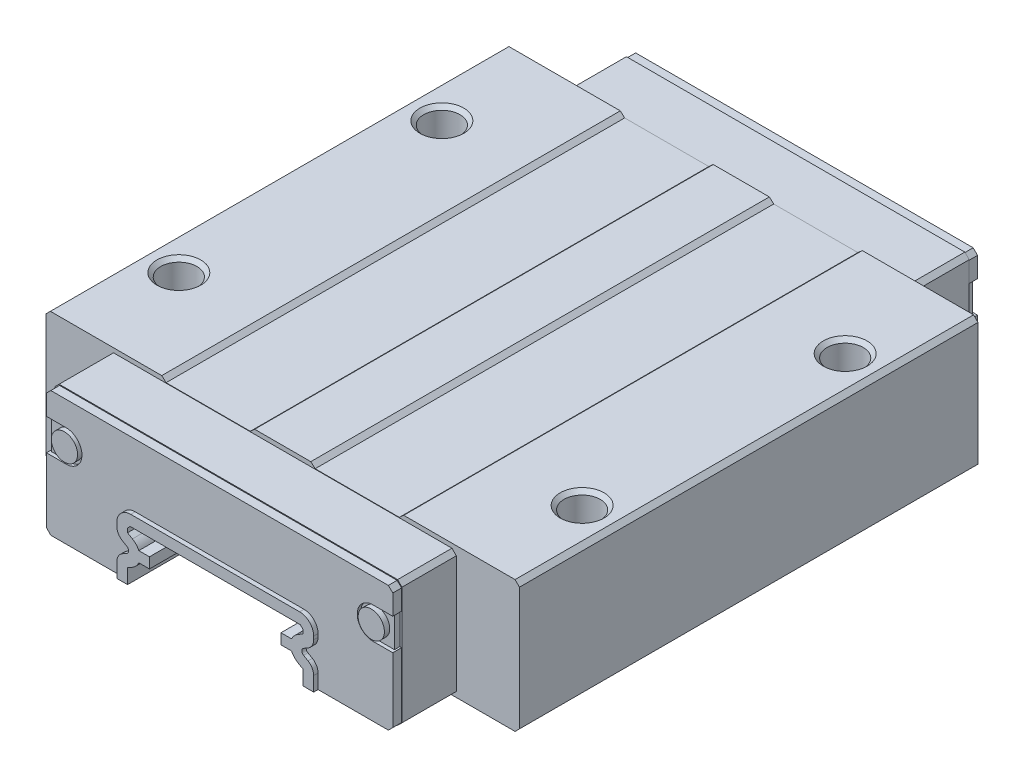
SolidWorks part; units mm, degrees
ref_plane "Front Plane" through (0, 0, 0) normal (0, 0, 1) x (1, 0, 0)
ref_plane "Top Plane" through (0, 0, 0) normal (0, 1, 0) x (1, 0, 0)
ref_plane "Right Plane" through (0, 0, 0) normal (1, 0, 0) x (0, 0, -1)
ref_plane "Plane1" through (0, 0, 0) normal (0, 0, 1) x (1, 0, 0)
sketch "Sketch1" plane through (0, 0, 0) normal (0, 0, 1) x (1, 0, 0)
  line L0 (-27, 19.5) -> (-27, 5.5)
  line L1 (-27, 5.5) -> (-26.5, 5)
  line L2 (-26.5, 5) -> (-14.4723, 5)
  line L3 (-14.4723, 5) -> (-14.2578, 5.1)
  line L4 (-14.2578, 5.1) -> (14.2578, 5.1)
  line L5 (14.2578, 5.1) -> (14.4723, 5)
  line L6 (14.4723, 5) -> (26.5, 5)
  line L7 (26.5, 5) -> (27, 5.5)
  line L8 (27, 5.5) -> (27, 19.5)
  line L9 (27, 19.5) -> (26.5, 20)
  line L10 (26.5, 20) -> (13.8, 20)
  line L11 (13.8, 20) -> (13.3, 19.55)
  line L12 (13.3, 19.55) -> (3.7, 19.55)
  line L13 (3.7, 19.55) -> (3.2, 20)
  line L14 (3.2, 20) -> (-3.2, 20)
  line L15 (-3.2, 20) -> (-3.7, 19.55)
  line L16 (-3.7, 19.55) -> (-13.3, 19.55)
  line L17 (-13.3, 19.55) -> (-13.8, 20)
  line L18 (-13.8, 20) -> (-26.5, 20)
  line L19 (-26.5, 20) -> (-27, 19.5)
extrude "Boss-Extrude1" add sketch "Sketch1" against normal blind 26.15 and the other way blind 26.15
ref_plane "Plane2" through (0, 0, 26.15) normal (0, 0, 1) x (1, 0, 0)
sketch "Sketch2" plane through (0, 0, 26.15) normal (0, 0, 1) x (1, 0, 0)
  line L0 (-19.8, 5.6) -> (-19.3, 5.1)
  line L1 (-19.3, 5.1) -> (19.3, 5.1)
  line L2 (19.3, 5.1) -> (19.8, 5.6)
  line L3 (19.8, 5.6) -> (19.8, 19)
  line L4 (19.8, 19) -> (19.3, 19.5)
  line L5 (19.3, 19.5) -> (-19.3, 19.5)
  line L6 (-19.3, 19.5) -> (-19.8, 19)
  line L7 (-19.8, 19) -> (-19.8, 5.6)
extrude "Boss-Extrude2" add sketch "Sketch2" along normal blind 7.7
ref_plane "Plane3" through (0, 0, -26.15) normal (0, 0, 1) x (1, 0, 0)
sketch "Sketch3" plane through (0, 0, -26.15) normal (0, 0, 1) x (1, 0, 0)
  line L0 (-19.8, 5.6) -> (-19.3, 5.1)
  line L1 (-19.3, 5.1) -> (19.3, 5.1)
  line L2 (19.3, 5.1) -> (19.8, 5.6)
  line L3 (19.8, 5.6) -> (19.8, 19)
  line L4 (19.8, 19) -> (19.3, 19.5)
  line L5 (19.3, 19.5) -> (-19.3, 19.5)
  line L6 (-19.3, 19.5) -> (-19.8, 19)
  line L7 (-19.8, 19) -> (-19.8, 5.6)
extrude "Boss-Extrude3" add sketch "Sketch3" against normal blind 7.7
ref_plane "Plane4" through (0, 0, 33.85) normal (0, 0, 1) x (1, 0, 0)
sketch "Sketch4" plane through (0, 0, 33.85) normal (0, 0, 1) x (1, 0, 0)
  line L0 (-54, 0) -> (54, 0)
  line L1 (54, 0) -> (54, 30)
  line L2 (54, 30) -> (-54, 30)
  line L3 (-54, 30) -> (-54, 0)
  line L4 (-19.75, 5.6) -> (-19.25, 5.1)
  line L5 (-19.25, 5.1) -> (19.25, 5.1)
  line L6 (19.25, 5.1) -> (19.75, 5.6)
  line L7 (19.75, 5.6) -> (19.75, 13)
  line L8 (19.75, 13) -> (17.5, 13)
  line L9 (17.5, 16.6) -> (19.75, 16.6)
  line L10 (19.75, 16.6) -> (19.75, 18.9)
  line L11 (19.75, 18.9) -> (19.25, 19.4)
  line L12 (19.25, 19.4) -> (-19.25, 19.4)
  line L13 (-19.25, 19.4) -> (-19.75, 18.9)
  line L14 (-19.75, 18.9) -> (-19.75, 16.6)
  line L15 (-19.75, 16.6) -> (-17.5, 16.6)
  line L16 (-17.5, 13) -> (-19.75, 13)
  line L17 (-19.75, 13) -> (-19.75, 5.6)
  arc A0 (17.5, 13) -> (17.5, 16.6) centre (17.5, 14.8) cw
  arc A1 (-17.5, 16.6) -> (-17.5, 13) centre (-17.5, 14.8) cw
extrude "Cut-Extrude1" cut sketch "Sketch4" against normal blind 1.5
ref_plane "Plane5" through (0, 0, 33.85) normal (0, 0, 1) x (1, 0, 0)
sketch "Sketch5" plane through (0, 0, 33.85) normal (0, 0, 1) x (1, 0, 0)
  line L0 (-54, 0) -> (54, 0)
  line L1 (54, 0) -> (54, 30)
  line L2 (54, 30) -> (-54, 30)
  line L3 (-54, 30) -> (-54, 0)
  line L4 (-11.23, 5.1) -> (11.23, 5.1)
  line L5 (11.23, 5.1) -> (11.23, 6.7357)
  line L6 (10.5801, 7.8615) -> (10.0742, 8.1536)
  line L7 (10.0742, 8.8464) -> (10.5801, 9.1385)
  line L8 (11.23, 10.2643) -> (11.23, 10.63)
  line L9 (9.63, 12.23) -> (-9.63, 12.23)
  line L10 (-11.23, 10.63) -> (-11.23, 10.2643)
  line L11 (-10.5801, 9.1385) -> (-10.0742, 8.8464)
  line L12 (-10.0742, 8.1536) -> (-10.5801, 7.8615)
  line L13 (-11.23, 6.7357) -> (-11.23, 5.1)
  arc A0 (11.23, 6.7357) -> (10.5801, 7.8615) centre (9.93, 6.7357) ccw
  arc A1 (10.0742, 8.1536) -> (10.0742, 8.8464) centre (10.2742, 8.5) cw
  arc A2 (10.5801, 9.1385) -> (11.23, 10.2643) centre (9.93, 10.2643) ccw
  arc A3 (11.23, 10.63) -> (9.63, 12.23) centre (9.63, 10.63) ccw
  arc A4 (-9.63, 12.23) -> (-11.23, 10.63) centre (-9.63, 10.63) ccw
  arc A5 (-11.23, 10.2643) -> (-10.5801, 9.1385) centre (-9.93, 10.2643) ccw
  arc A6 (-10.0742, 8.8464) -> (-10.0742, 8.1536) centre (-10.2742, 8.5) cw
  arc A7 (-10.5801, 7.8615) -> (-11.23, 6.7357) centre (-9.93, 6.7357) ccw
extrude "Cut-Extrude2" cut sketch "Sketch5" against normal blind 0.5
ref_plane "Plane6" through (0, 0, -33.85) normal (0, 0, 1) x (1, 0, 0)
sketch "Sketch6" plane through (0, 0, -33.85) normal (0, 0, 1) x (1, 0, 0)
  line L0 (-54, 0) -> (54, 0)
  line L1 (54, 0) -> (54, 30)
  line L2 (54, 30) -> (-54, 30)
  line L3 (-54, 30) -> (-54, 0)
  line L4 (-19.75, 5.6) -> (-19.25, 5.1)
  line L5 (-19.25, 5.1) -> (19.25, 5.1)
  line L6 (19.25, 5.1) -> (19.75, 5.6)
  line L7 (19.75, 5.6) -> (19.75, 13)
  line L8 (19.75, 13) -> (17.5, 13)
  line L9 (17.5, 16.6) -> (19.75, 16.6)
  line L10 (19.75, 16.6) -> (19.75, 18.9)
  line L11 (19.75, 18.9) -> (19.25, 19.4)
  line L12 (19.25, 19.4) -> (-19.25, 19.4)
  line L13 (-19.25, 19.4) -> (-19.75, 18.9)
  line L14 (-19.75, 18.9) -> (-19.75, 16.6)
  line L15 (-19.75, 16.6) -> (-17.5, 16.6)
  line L16 (-17.5, 13) -> (-19.75, 13)
  line L17 (-19.75, 13) -> (-19.75, 5.6)
  arc A0 (17.5, 13) -> (17.5, 16.6) centre (17.5, 14.8) cw
  arc A1 (-17.5, 16.6) -> (-17.5, 13) centre (-17.5, 14.8) cw
extrude "Cut-Extrude3" cut sketch "Sketch6" along normal blind 1.5
ref_plane "Plane7" through (0, 0, -33.85) normal (0, 0, 1) x (1, 0, 0)
sketch "Sketch7" plane through (0, 0, -33.85) normal (0, 0, 1) x (1, 0, 0)
  line L0 (-54, 0) -> (54, 0)
  line L1 (54, 0) -> (54, 30)
  line L2 (54, 30) -> (-54, 30)
  line L3 (-54, 30) -> (-54, 0)
  line L4 (-11.23, 5.1) -> (11.23, 5.1)
  line L5 (11.23, 5.1) -> (11.23, 6.7357)
  line L6 (10.5801, 7.8615) -> (10.0742, 8.1536)
  line L7 (10.0742, 8.8464) -> (10.5801, 9.1385)
  line L8 (11.23, 10.2643) -> (11.23, 10.63)
  line L9 (9.63, 12.23) -> (-9.63, 12.23)
  line L10 (-11.23, 10.63) -> (-11.23, 10.2643)
  line L11 (-10.5801, 9.1385) -> (-10.0742, 8.8464)
  line L12 (-10.0742, 8.1536) -> (-10.5801, 7.8615)
  line L13 (-11.23, 6.7357) -> (-11.23, 5.1)
  arc A0 (11.23, 6.7357) -> (10.5801, 7.8615) centre (9.93, 6.7357) ccw
  arc A1 (10.0742, 8.1536) -> (10.0742, 8.8464) centre (10.2742, 8.5) cw
  arc A2 (10.5801, 9.1385) -> (11.23, 10.2643) centre (9.93, 10.2643) ccw
  arc A3 (11.23, 10.63) -> (9.63, 12.23) centre (9.63, 10.63) ccw
  arc A4 (-9.63, 12.23) -> (-11.23, 10.63) centre (-9.63, 10.63) ccw
  arc A5 (-11.23, 10.2643) -> (-10.5801, 9.1385) centre (-9.93, 10.2643) ccw
  arc A6 (-10.0742, 8.8464) -> (-10.0742, 8.1536) centre (-10.2742, 8.5) cw
  arc A7 (-10.5801, 7.8615) -> (-11.23, 6.7357) centre (-9.93, 6.7357) ccw
extrude "Cut-Extrude4" cut sketch "Sketch7" along normal blind 0.5
ref_plane "Plane8" through (0, 0, 32.35) normal (0, 0, 1) x (1, 0, 0)
sketch "Sketch8" plane through (0, 0, 32.35) normal (0, 0, 1) x (1, 0, 0)
  line L0 (-19.55, 13) -> (-17.5, 13)
  line L1 (-17.5, 16.6) -> (-19.55, 16.6)
  line L2 (-19.55, 16.6) -> (-19.55, 13)
  arc A0 (-17.5, 13) -> (-17.5, 16.6) centre (-17.5, 14.8) ccw
extrude "Boss-Extrude4" add sketch "Sketch8" along normal blind 0.6
ref_plane "Plane9" through (0, 0, 32.35) normal (0, 0, 1) x (1, 0, 0)
sketch "Sketch9" plane through (0, 0, 32.35) normal (0, 0, 1) x (1, 0, 0)
  line L0 (17.5, 13) -> (19.55, 13)
  line L1 (19.55, 13) -> (19.55, 16.6)
  line L2 (19.55, 16.6) -> (17.5, 16.6)
  arc A0 (17.5, 16.6) -> (17.5, 13) centre (17.5, 14.8) ccw
extrude "Boss-Extrude5" add sketch "Sketch9" along normal blind 0.6
ref_plane "Plane10" through (0, 0, -32.35) normal (0, 0, 1) x (1, 0, 0)
sketch "Sketch10" plane through (0, 0, -32.35) normal (0, 0, 1) x (1, 0, 0)
  line L0 (-19.55, 13) -> (-17.5, 13)
  line L1 (-17.5, 16.6) -> (-19.55, 16.6)
  line L2 (-19.55, 16.6) -> (-19.55, 13)
  arc A0 (-17.5, 13) -> (-17.5, 16.6) centre (-17.5, 14.8) ccw
extrude "Boss-Extrude6" add sketch "Sketch10" against normal blind 0.6
ref_plane "Plane11" through (0, 0, -32.35) normal (0, 0, 1) x (1, 0, 0)
sketch "Sketch11" plane through (0, 0, -32.35) normal (0, 0, 1) x (1, 0, 0)
  line L0 (17.5, 13) -> (19.55, 13)
  line L1 (19.55, 13) -> (19.55, 16.6)
  line L2 (19.55, 16.6) -> (17.5, 16.6)
  arc A0 (17.5, 16.6) -> (17.5, 13) centre (17.5, 14.8) ccw
extrude "Boss-Extrude7" add sketch "Sketch11" against normal blind 0.6
ref_plane "Plane12" through (-17.5, 0, 0) normal (1, 0, 0) x (0, 0, -1)
sketch "Sketch12" plane through (-17.5, 0, 0) normal (1, 0, 0) x (0, 0, -1)
  line L0 (-33.55, 14.8) -> (-33.55, 16.3)
  line L1 (-33.55, 16.3) -> (-32.95, 16.3)
  line L2 (-32.95, 16.3) -> (-32.95, 14.8)
  line L3 (-32.95, 14.8) -> (-33.55, 14.8)
  line L4 (-32.95, 14.8) -> (-33.55, 14.8) construction
revolve "Revolve1" add sketch "Sketch12" angle 360 about L4 reverse direction yes
ref_plane "Plane13" through (-17.5, 0, 0) normal (1, 0, 0) x (0, 0, -1)
sketch "Sketch13" plane through (-17.5, 0, 0) normal (1, 0, 0) x (0, 0, -1)
  line L0 (32.95, 14.8) -> (32.95, 16.3)
  line L1 (32.95, 16.3) -> (33.55, 16.3)
  line L2 (33.55, 16.3) -> (33.55, 14.8)
  line L3 (33.55, 14.8) -> (32.95, 14.8)
  line L4 (33.55, 14.8) -> (32.95, 14.8) construction
revolve "Revolve2" add sketch "Sketch13" angle 360 about L4 reverse direction yes
ref_plane "Plane14" through (17.5, 0, 0) normal (1, 0, 0) x (0, 0, -1)
sketch "Sketch14" plane through (17.5, 0, 0) normal (1, 0, 0) x (0, 0, -1)
  line L0 (-33.55, 14.8) -> (-33.55, 16.3)
  line L1 (-33.55, 16.3) -> (-32.95, 16.3)
  line L2 (-32.95, 16.3) -> (-32.95, 14.8)
  line L3 (-32.95, 14.8) -> (-33.55, 14.8)
  line L4 (-32.95, 14.8) -> (-33.55, 14.8) construction
revolve "Revolve3" add sketch "Sketch14" angle 360 about L4 reverse direction yes
ref_plane "Plane15" through (17.5, 0, 0) normal (1, 0, 0) x (0, 0, -1)
sketch "Sketch15" plane through (17.5, 0, 0) normal (1, 0, 0) x (0, 0, -1)
  line L0 (32.95, 14.8) -> (32.95, 16.3)
  line L1 (32.95, 16.3) -> (33.55, 16.3)
  line L2 (33.55, 16.3) -> (33.55, 14.8)
  line L3 (33.55, 14.8) -> (32.95, 14.8)
  line L4 (33.55, 14.8) -> (32.95, 14.8) construction
revolve "Revolve4" add sketch "Sketch15" angle 360 about L4 reverse direction yes
ref_plane "Plane16" through (0, 0, 0) normal (0, 0, 1) x (1, 0, 0)
sketch "Sketch16" plane through (0, 0, 0) normal (0, 0, 1) x (1, 0, 0)
  line L0 (-10, 6.7761) -> (-10, 0.5)
  line L1 (-10, 0.5) -> (-9.5, 0)
  line L2 (-9.5, 0) -> (9.5, 0)
  line L3 (9.5, 0) -> (10, 0.5)
  line L4 (10, 0.5) -> (10, 6.7761)
  line L5 (10, 6.7761) -> (9.44, 7.0994)
  line L6 (8.7177, 7.9) -> (7.5, 7.9)
  line L7 (7.5, 7.9) -> (7.5, 9.1)
  line L8 (7.5, 9.1) -> (8.7177, 9.1)
  line L9 (9.44, 9.9006) -> (10, 10.2238)
  line L10 (10, 10.2238) -> (10, 10.7)
  line L11 (10, 10.7) -> (9.7, 11)
  line L12 (9.7, 11) -> (-9.7, 11)
  line L13 (-9.7, 11) -> (-10, 10.7)
  line L14 (-10, 10.7) -> (-10, 10.2238)
  line L15 (-10, 10.2238) -> (-9.44, 9.9006)
  line L16 (-8.7177, 9.1) -> (-7.5, 9.1)
  line L17 (-7.5, 9.1) -> (-7.5, 7.9)
  line L18 (-7.5, 7.9) -> (-8.7177, 7.9)
  line L19 (-9.44, 7.0994) -> (-10, 6.7761)
  arc A0 (9.44, 7.0994) -> (8.7177, 7.9) centre (10.315, 8.615) cw
  arc A1 (8.7177, 9.1) -> (9.44, 9.9006) centre (10.315, 8.385) cw
  arc A2 (-9.44, 9.9006) -> (-8.7177, 9.1) centre (-10.315, 8.385) cw
  arc A3 (-8.7177, 7.9) -> (-9.44, 7.0994) centre (-10.315, 8.615) cw
extrude "Cut-Extrude5" cut sketch "Sketch16" against normal blind 26.15 and the other way blind 26.15
ref_plane "Plane17" through (0, 0, 26.15) normal (0, 0, 1) x (1, 0, 0)
sketch "Sketch17" plane through (0, 0, 26.15) normal (0, 0, 1) x (1, 0, 0)
  line L0 (-10, 6.7761) -> (-10, 0.5)
  line L1 (-10, 0.5) -> (-9.5, 0)
  line L2 (-9.5, 0) -> (9.5, 0)
  line L3 (9.5, 0) -> (10, 0.5)
  line L4 (10, 0.5) -> (10, 6.7761)
  line L5 (10, 6.7761) -> (9.44, 7.0994)
  line L6 (8.7177, 7.9) -> (7.5, 7.9)
  line L7 (7.5, 7.9) -> (7.5, 9.1)
  line L8 (7.5, 9.1) -> (8.7177, 9.1)
  line L9 (9.44, 9.9006) -> (10, 10.2238)
  line L10 (10, 10.2238) -> (10, 10.7)
  line L11 (10, 10.7) -> (9.7, 11)
  line L12 (9.7, 11) -> (-9.7, 11)
  line L13 (-9.7, 11) -> (-10, 10.7)
  line L14 (-10, 10.7) -> (-10, 10.2238)
  line L15 (-10, 10.2238) -> (-9.44, 9.9006)
  line L16 (-8.7177, 9.1) -> (-7.5, 9.1)
  line L17 (-7.5, 9.1) -> (-7.5, 7.9)
  line L18 (-7.5, 7.9) -> (-8.7177, 7.9)
  line L19 (-9.44, 7.0994) -> (-10, 6.7761)
  arc A0 (9.44, 7.0994) -> (8.7177, 7.9) centre (10.315, 8.615) cw
  arc A1 (8.7177, 9.1) -> (9.44, 9.9006) centre (10.315, 8.385) cw
  arc A2 (-9.44, 9.9006) -> (-8.7177, 9.1) centre (-10.315, 8.385) cw
  arc A3 (-8.7177, 7.9) -> (-9.44, 7.0994) centre (-10.315, 8.615) cw
extrude "Cut-Extrude6" cut sketch "Sketch17" along normal blind 26.15
ref_plane "Plane18" through (0, 0, 26.15) normal (0, 0, 1) x (1, 0, 0)
sketch "Sketch18" plane through (0, 0, 26.15) normal (0, 0, 1) x (1, 0, 0)
  line L0 (-54, 0) -> (54, 0)
  line L1 (54, 0) -> (54, 30)
  line L2 (54, 30) -> (-54, 30)
  line L3 (-54, 30) -> (-54, 0)
  line L4 (-19.8, 5.55) -> (-19.35, 5.1)
  line L5 (-19.35, 5.1) -> (-10.05, 5.1)
  line L6 (-10.05, 5.1) -> (-10.05, 6.8261)
  line L7 (-10.05, 6.8261) -> (-9.5074, 7.1191)
  line L8 (-8.7505, 7.95) -> (-7.55, 7.95)
  line L9 (-7.55, 7.95) -> (-7.55, 9.05)
  line L10 (-7.55, 9.05) -> (-8.7505, 9.05)
  line L11 (-9.5074, 9.8809) -> (-10.05, 10.1738)
  line L12 (-10.05, 10.1738) -> (-10.05, 10.75)
  line L13 (-10.05, 10.75) -> (-9.75, 11.05)
  line L14 (-9.75, 11.05) -> (9.75, 11.05)
  line L15 (9.75, 11.05) -> (10.05, 10.75)
  line L16 (10.05, 10.75) -> (10.05, 10.1738)
  line L17 (10.05, 10.1738) -> (9.5074, 9.8809)
  line L18 (8.7505, 9.05) -> (7.55, 9.05)
  line L19 (7.55, 9.05) -> (7.55, 7.95)
  line L20 (7.55, 7.95) -> (8.7505, 7.95)
  line L21 (9.5074, 7.1191) -> (10.05, 6.8261)
  line L22 (10.05, 6.8261) -> (10.05, 5.1)
  line L23 (10.05, 5.1) -> (19.35, 5.1)
  line L24 (19.35, 5.1) -> (19.8, 5.55)
  line L25 (19.8, 5.55) -> (19.8, 19.05)
  line L26 (19.8, 19.05) -> (19.35, 19.5)
  line L27 (19.35, 19.5) -> (-19.35, 19.5)
  line L28 (-19.35, 19.5) -> (-19.8, 19.05)
  line L29 (-19.8, 19.05) -> (-19.8, 5.55)
  arc A0 (-9.5074, 7.1191) -> (-8.7505, 7.95) centre (-10.315, 8.615) ccw
  arc A1 (-8.7505, 9.05) -> (-9.5074, 9.8809) centre (-10.315, 8.385) ccw
  arc A2 (9.5074, 9.8809) -> (8.7505, 9.05) centre (10.315, 8.385) ccw
  arc A3 (8.7505, 7.95) -> (9.5074, 7.1191) centre (10.315, 8.615) ccw
extrude "Cut-Extrude7" cut sketch "Sketch18" along normal blind 0.05
ref_plane "Plane19" through (0, 0, -26.15) normal (0, 0, 1) x (1, 0, 0)
sketch "Sketch19" plane through (0, 0, -26.15) normal (0, 0, 1) x (1, 0, 0)
  line L0 (-10, 6.7761) -> (-10, 0.5)
  line L1 (-10, 0.5) -> (-9.5, 0)
  line L2 (-9.5, 0) -> (9.5, 0)
  line L3 (9.5, 0) -> (10, 0.5)
  line L4 (10, 0.5) -> (10, 6.7761)
  line L5 (10, 6.7761) -> (9.44, 7.0994)
  line L6 (8.7177, 7.9) -> (7.5, 7.9)
  line L7 (7.5, 7.9) -> (7.5, 9.1)
  line L8 (7.5, 9.1) -> (8.7177, 9.1)
  line L9 (9.44, 9.9006) -> (10, 10.2238)
  line L10 (10, 10.2238) -> (10, 10.7)
  line L11 (10, 10.7) -> (9.7, 11)
  line L12 (9.7, 11) -> (-9.7, 11)
  line L13 (-9.7, 11) -> (-10, 10.7)
  line L14 (-10, 10.7) -> (-10, 10.2238)
  line L15 (-10, 10.2238) -> (-9.44, 9.9006)
  line L16 (-8.7177, 9.1) -> (-7.5, 9.1)
  line L17 (-7.5, 9.1) -> (-7.5, 7.9)
  line L18 (-7.5, 7.9) -> (-8.7177, 7.9)
  line L19 (-9.44, 7.0994) -> (-10, 6.7761)
  arc A0 (9.44, 7.0994) -> (8.7177, 7.9) centre (10.315, 8.615) cw
  arc A1 (8.7177, 9.1) -> (9.44, 9.9006) centre (10.315, 8.385) cw
  arc A2 (-9.44, 9.9006) -> (-8.7177, 9.1) centre (-10.315, 8.385) cw
  arc A3 (-8.7177, 7.9) -> (-9.44, 7.0994) centre (-10.315, 8.615) cw
extrude "Cut-Extrude8" cut sketch "Sketch19" against normal blind 26.15
ref_plane "Plane20" through (0, 0, -26.15) normal (0, 0, 1) x (1, 0, 0)
sketch "Sketch20" plane through (0, 0, -26.15) normal (0, 0, 1) x (1, 0, 0)
  line L0 (-54, 0) -> (54, 0)
  line L1 (54, 0) -> (54, 30)
  line L2 (54, 30) -> (-54, 30)
  line L3 (-54, 30) -> (-54, 0)
  line L4 (-19.8, 5.55) -> (-19.35, 5.1)
  line L5 (-19.35, 5.1) -> (-10.05, 5.1)
  line L6 (-10.05, 5.1) -> (-10.05, 6.8261)
  line L7 (-10.05, 6.8261) -> (-9.5074, 7.1191)
  line L8 (-8.7505, 7.95) -> (-7.55, 7.95)
  line L9 (-7.55, 7.95) -> (-7.55, 9.05)
  line L10 (-7.55, 9.05) -> (-8.7505, 9.05)
  line L11 (-9.5074, 9.8809) -> (-10.05, 10.1738)
  line L12 (-10.05, 10.1738) -> (-10.05, 10.75)
  line L13 (-10.05, 10.75) -> (-9.75, 11.05)
  line L14 (-9.75, 11.05) -> (9.75, 11.05)
  line L15 (9.75, 11.05) -> (10.05, 10.75)
  line L16 (10.05, 10.75) -> (10.05, 10.1738)
  line L17 (10.05, 10.1738) -> (9.5074, 9.8809)
  line L18 (8.7505, 9.05) -> (7.55, 9.05)
  line L19 (7.55, 9.05) -> (7.55, 7.95)
  line L20 (7.55, 7.95) -> (8.7505, 7.95)
  line L21 (9.5074, 7.1191) -> (10.05, 6.8261)
  line L22 (10.05, 6.8261) -> (10.05, 5.1)
  line L23 (10.05, 5.1) -> (19.35, 5.1)
  line L24 (19.35, 5.1) -> (19.8, 5.55)
  line L25 (19.8, 5.55) -> (19.8, 19.05)
  line L26 (19.8, 19.05) -> (19.35, 19.5)
  line L27 (19.35, 19.5) -> (-19.35, 19.5)
  line L28 (-19.35, 19.5) -> (-19.8, 19.05)
  line L29 (-19.8, 19.05) -> (-19.8, 5.55)
  arc A0 (-9.5074, 7.1191) -> (-8.7505, 7.95) centre (-10.315, 8.615) ccw
  arc A1 (-8.7505, 9.05) -> (-9.5074, 9.8809) centre (-10.315, 8.385) ccw
  arc A2 (9.5074, 9.8809) -> (8.7505, 9.05) centre (10.315, 8.385) ccw
  arc A3 (8.7505, 7.95) -> (9.5074, 7.1191) centre (10.315, 8.615) ccw
extrude "Cut-Extrude9" cut sketch "Sketch20" against normal blind 0.05
ref_plane "Plane21" through (-23, 0, 0) normal (1, 0, 0) x (0, 0, -1)
sketch "Sketch21" plane through (-23, 0, 0) normal (1, 0, 0) x (0, 0, -1)
  line L0 (15, 20) -> (17.5, 20)
  line L1 (17.5, 20) -> (17.067, 19.567)
  line L2 (17.067, 19.567) -> (17.067, 5.433)
  line L3 (17.067, 5.433) -> (17.5, 5)
  line L4 (17.5, 5) -> (15, 5)
  line L5 (15, 5) -> (15, 20)
  line L6 (15, 5) -> (15, 20) construction
revolve "Cut-Revolve1" cut sketch "Sketch21" angle 360 about L6 reverse direction yes
ref_plane "Plane22" through (23, 0, 0) normal (1, 0, 0) x (0, 0, -1)
sketch "Sketch22" plane through (23, 0, 0) normal (1, 0, 0) x (0, 0, -1)
  line L0 (15, 20) -> (17.5, 20)
  line L1 (17.5, 20) -> (17.067, 19.567)
  line L2 (17.067, 19.567) -> (17.067, 5.433)
  line L3 (17.067, 5.433) -> (17.5, 5)
  line L4 (17.5, 5) -> (15, 5)
  line L5 (15, 5) -> (15, 20)
  line L6 (15, 5) -> (15, 20) construction
revolve "Cut-Revolve2" cut sketch "Sketch22" angle 360 about L6 reverse direction yes
ref_plane "Plane23" through (-23, 0, 0) normal (1, 0, 0) x (0, 0, -1)
sketch "Sketch23" plane through (-23, 0, 0) normal (1, 0, 0) x (0, 0, -1)
  line L0 (-15, 20) -> (-12.5, 20)
  line L1 (-12.5, 20) -> (-12.933, 19.567)
  line L2 (-12.933, 19.567) -> (-12.933, 5.433)
  line L3 (-12.933, 5.433) -> (-12.5, 5)
  line L4 (-12.5, 5) -> (-15, 5)
  line L5 (-15, 5) -> (-15, 20)
  line L6 (-15, 5) -> (-15, 20) construction
revolve "Cut-Revolve3" cut sketch "Sketch23" angle 360 about L6 reverse direction yes
ref_plane "Plane24" through (23, 0, 0) normal (1, 0, 0) x (0, 0, -1)
sketch "Sketch24" plane through (23, 0, 0) normal (1, 0, 0) x (0, 0, -1)
  line L0 (-15, 20) -> (-12.5, 20)
  line L1 (-12.5, 20) -> (-12.933, 19.567)
  line L2 (-12.933, 19.567) -> (-12.933, 5.433)
  line L3 (-12.933, 5.433) -> (-12.5, 5)
  line L4 (-12.5, 5) -> (-15, 5)
  line L5 (-15, 5) -> (-15, 20)
  line L6 (-15, 5) -> (-15, 20) construction
revolve "Cut-Revolve4" cut sketch "Sketch24" angle 360 about L6 reverse direction yes
